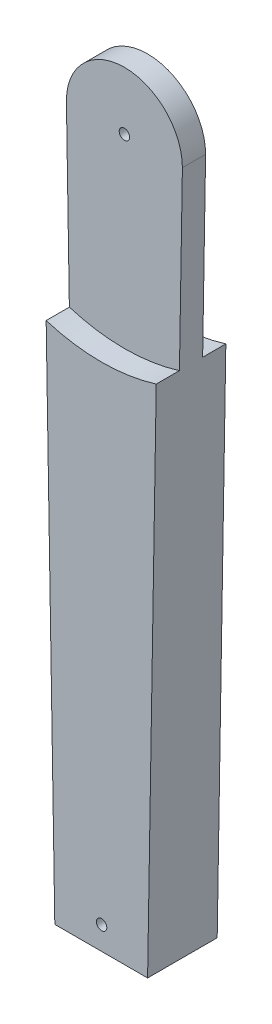
SolidWorks part; units mm, degrees
ref_plane "Front Plane" through (0, 0, 0) normal (0, 0, 1) x (1, 0, 0)
ref_plane "Top Plane" through (0, 0, 0) normal (0, 1, 0) x (1, 0, 0)
ref_plane "Right Plane" through (0, 0, 0) normal (1, 0, 0) x (0, 0, -1)
sketch "Sketch7" plane through (0, 0, 0) normal (0, 0, 1) x (1, 0, 0)
  line L0 (-25, 0) -> (-20, -300)
  line L1 (-20, -300) -> (20, -300)
  line L2 (25, 0) -> (20, -300)
  arc A0 (25, 0) -> (-25, 0) centre (0, 0) ccw
  arc A1 (-24.9861, -0.8331) -> (24.9861, -0.8331) centre (0, 0) ccw
  point P9 (0, -300)
  dimension "D2" = 50
  dimension "D1" = 300
  dimension "D3" = 40
extrude "Boss-Extrude3" add sketch "Sketch7" along normal mid plane 30 contours L0 A1 L2 A0 | A1 L0 L1 L2 region at (0, 0, 0) region at (0, -154.9404, 0)
sketch "Sketch10" plane through (0, 0, 15) normal (0, 0, 1) x (1, 0, 0)
  line L0 (-50, 0) -> (-45, -100)
  line L1 (-45, -100) -> (45, -100)
  line L2 (50, 0) -> (45, -100)
  line L3 (0, 0) -> (0, -100)
  arc A0 (50, 0) -> (-50, 0) centre (0, 0) ccw
  arc A1 (-49.7506, -4.9875) -> (49.7506, -4.9875) centre (0, 0) ccw
  line M6 (-25, 0) -> (-20, -300)
  line M8 (20, -300) -> (25, 0)
  arc M9 (25, 0) -> (-25, 0) centre (0, 0) ccw
  dimension "D2" = 100
extrude "Cut-Extrude4" cut sketch "Sketch10" against normal blind 10 contours A1 M6 M8 M9 region at (-23.7345, -21.8419, 15)
ref_plane "Plane2" through (0, 0, 0) normal (0, 0, 1) x (1, 0, 0)
mirror "Mirror1" about plane through (0, 0, 0) normal (0, 0, 1) of "Cut-Extrude4"
sketch "Sketch11" plane through (0, 0, 5) normal (0, 0, 1) x (1, 0, 0)
  circle A0 centre (0, 0) radius 2.25
  dimension "D1" = 4.5
extrude "Cut-Extrude5" cut sketch "Sketch11" against normal blind 320
sketch "Sketch14" plane through (0, -300, 0) normal (0, -1, 0) x (1, 0, 0)
  line L1 (-10, -5) -> (10, -5)
  line L2 (-10, -5) -> (-10, 5)
  line L3 (-10, 5) -> (10, 5)
  line L4 (10, -5) -> (10, 5)
  line L5 (-10, -5) -> (10, 5) construction
  line L6 (-10, 5) -> (10, -5) construction
  point P0 (0, 0)
  dimension "D1" = 20
  dimension "D2" = 10
extrude "Cut-Extrude6" cut sketch "Sketch14" against normal blind 20
sketch "Sketch16" plane through (0, 0, -5) normal (0, 0, 1) x (1, 0, 0)
  line L0 (24.2714, -43.7138) -> (20, -300) construction
  line L2 (-20, -300) -> (20, -300) construction
  circle A0 centre (0.1639, -290) radius 2.25
  dimension "D3" = 4.5
  dimension "D1" = 20
  dimension "D2" = 10
extrude "Cut-Extrude7" cut sketch "Sketch16" against normal mid plane 125
sketch "Sketch17" plane through (0, 0, 15) normal (0, 0, 1) x (1, 0, 0)
  circle A0 centre (0, 0) radius 80
  dimension "D1" = 160
extrude "Cut-Extrude9" cut sketch "Sketch17" against normal blind 10
ref_plane "Plane3" through (0, 0, 0) normal (0, 0, -1) x (-1, 0, 0)
mirror "Mirror2" about plane through (0, 0, 0) normal (0, 0, -1) of "Cut-Extrude9"
